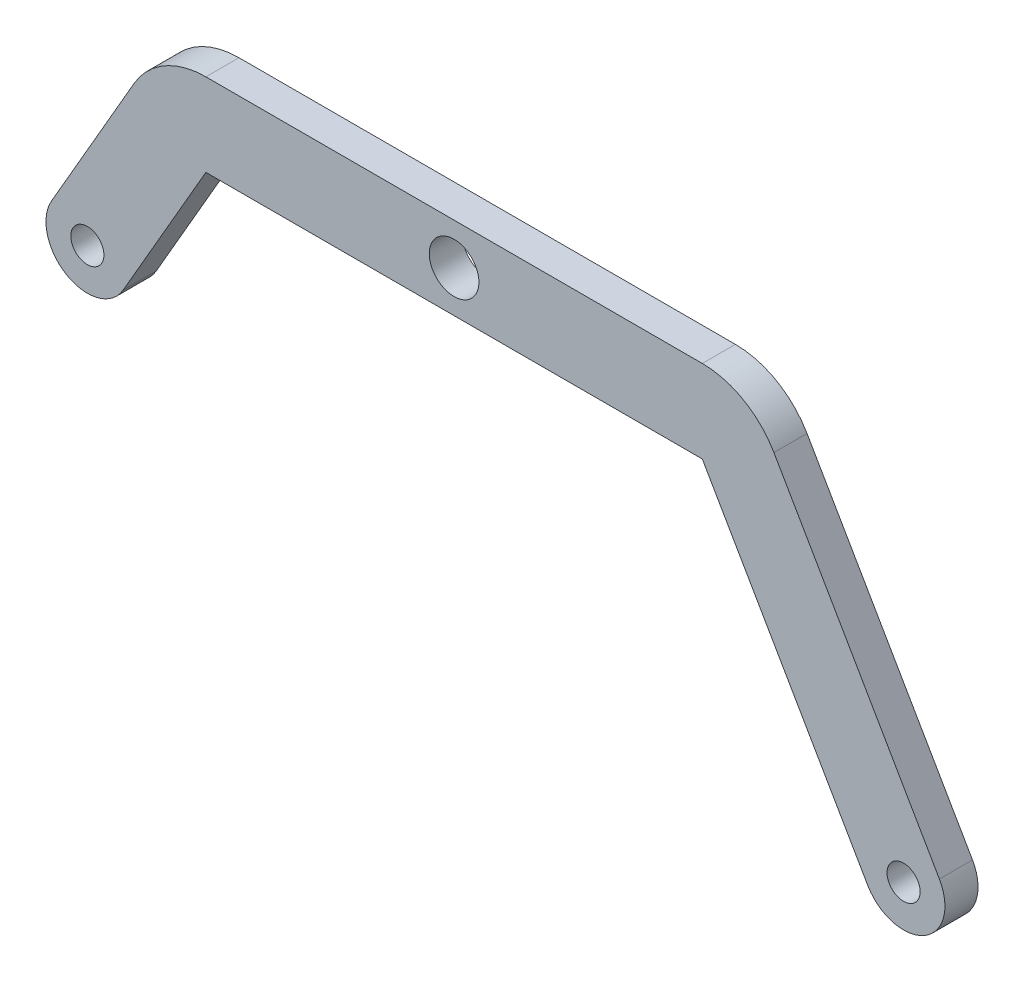
SolidWorks part; units mm, degrees
ref_plane "Front Plane" through (0, 0, 0) normal (0, 0, 1) x (1, 0, 0)
ref_plane "Top Plane" through (0, 0, 0) normal (0, 1, 0) x (1, 0, 0)
ref_plane "Right Plane" through (0, 0, 0) normal (1, 0, 0) x (0, 0, -1)
ref_axis "X" through (-88.99, 0, 0) along (1, 0, 0)
ref_axis "Y" through (0, 55, 0) along (0, -1, 0)
ref_axis "Z" through (0, 0, -88.99) along (0, 0, 1)
sketch "Sketch1" plane through (0, 0, 0) normal (0, 0, 1) x (1, 0, 0)
  line L0 (-75, -12.5) -> (75, -12.5)
  line L1 (-75, 12.5) -> (75, 12.5)
  line L3 (125, -99.1025) -> (75, -12.5)
  line L4 (-75, -12.5) -> (-100, -55.8013)
  line L5 (-121.6506, -43.3013) -> (-96.6506, 0)
  line L6 (96.6506, 0) -> (146.6506, -86.6025)
  line L7 (0, 12.5) -> (0, -12.5) construction
  arc A0 (146.6506, -86.6025) -> (125, -99.1025) centre (135.8253, -92.8525) cw
  arc A1 (-100, -55.8013) -> (-121.6506, -43.3013) centre (-110.8253, -49.5513) cw
  arc A2 (-96.6506, 0) -> (-75, 12.5) centre (-75, -12.5) cw
  arc A3 (75, 12.5) -> (96.6506, 0) centre (75, -12.5) cw
  circle A4 centre (0, 0) radius 7.5
  circle A5 centre (135.8253, -92.8525) radius 5
  circle A6 centre (-110.8253, -49.5513) radius 5
  point P3 (0, 0)
  dimension "D1" = 150
  dimension "D7" = 15
  dimension "D8" = 10
  dimension "D2" = 25
  dimension "D3" = 100
  dimension "D4" = 50
  dimension "D5" = 60
  dimension "D6" = 60
extrude "Boss-Extrude1" add sketch "Sketch1" along normal mid plane 10
